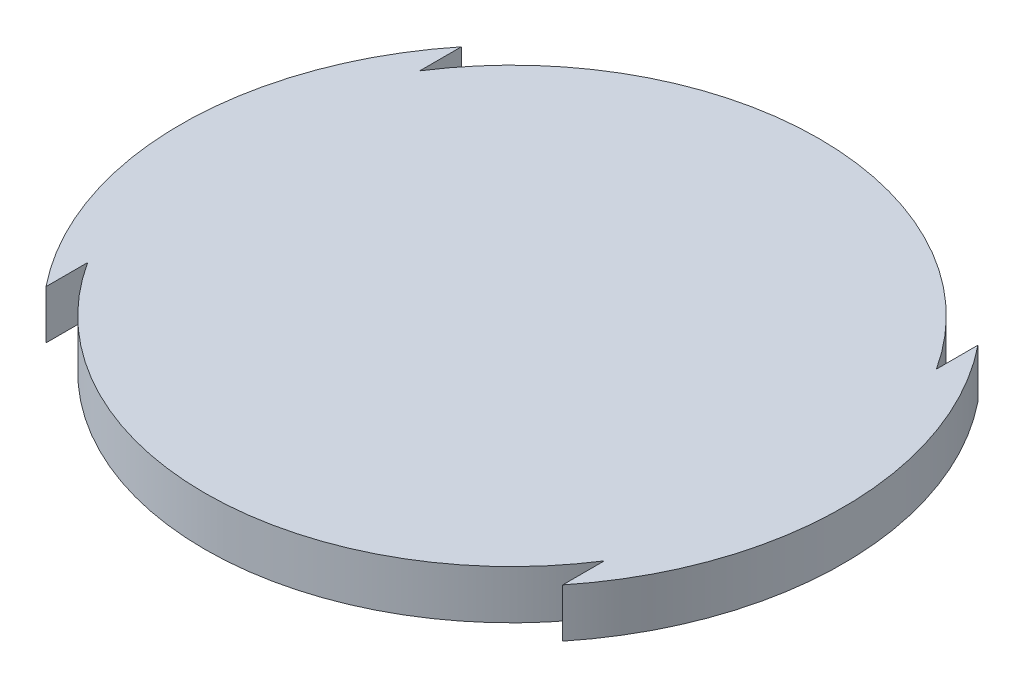
SolidWorks part; units mm, degrees
ref_plane "Front Plane" through (0, 0, 0) normal (0, 0, 1) x (1, 0, 0)
ref_plane "Top Plane" through (0, 0, 0) normal (0, 1, 0) x (1, 0, 0)
ref_plane "Right Plane" through (0, 0, 0) normal (1, 0, 0) x (0, 0, -1)
sketch "Sketch1" plane through (0, 0, 0) normal (0, 1, 0) x (1, 0, 0)
  circle A0 centre (0, 0) radius 68
  dimension "D1" = 136
extrude "Boss-Extrude1" add sketch "Sketch1" along normal blind 10
sketch "Sketch2" plane through (0, 10, 0) normal (0, 1, 0) x (1, 0, 0)
  line L0 (-53, -42.6028) -> (-53, -34.0588)
  line L1 (0, 37.0764) -> (0, -27.4787) construction
  line L2 (53, 42.6028) -> (53, 34.0588)
  line L3 (-53, 34.0588) -> (-53, 42.6028)
  line L4 (53, -34.0588) -> (53, -42.6028)
  arc A0 (-53, -34.0588) -> (53, -34.0588) centre (0, 0) ccw
  arc A1 (-53, -42.6028) -> (53, -42.6028) centre (0, 0) ccw
  circle A2 centre (0, 0) radius 68 construction
  arc A3 (53, 34.0588) -> (-53, 34.0588) centre (0, 0) ccw
  arc A4 (53, 42.6028) -> (-53, 42.6028) centre (0, 0) ccw
  dimension "D1" = 126
  dimension "D2" = 53
  dimension "D3" = 53
extrude "Cut-Extrude1" cut sketch "Sketch2" against normal up to surface (10 mm away) up to face at (0, 0, 68)
